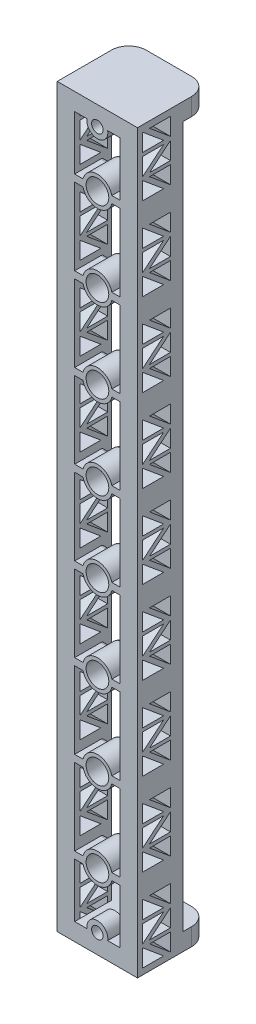
SolidWorks part; units mm, degrees
ref_plane "Front Plane" through (0, 0, 0) normal (0, 0, 1) x (1, 0, 0)
ref_plane "Top Plane" through (0, 0, 0) normal (0, 1, 0) x (1, 0, 0)
ref_plane "Right Plane" through (0, 0, 0) normal (1, 0, 0) x (0, 0, -1)
sketch "Sketch1" plane through (0, 0, 0) normal (0, 0, 1) x (1, 0, 0)
  line L0 (6.5, 100.5) -> (6.5, -100.5)
  line L1 (-11.5, 105.5) -> (11.5, 105.5)
  line L2 (-11.5, 105.5) -> (-11.5, -105.5)
  line L3 (-11.5, -105.5) -> (11.5, -105.5)
  line L4 (11.5, 105.5) -> (11.5, -105.5)
  line L5 (-11.5, 105.5) -> (11.5, -105.5) construction
  line L6 (-11.5, -105.5) -> (11.5, 105.5) construction
  line L7 (-6.5, -100.5) -> (6.5, -100.5)
  line L8 (-6.5, 100.5) -> (-6.5, -100.5)
  line L9 (-6.5, 100.5) -> (6.5, 100.5)
  point P0 (0, 0)
  dimension "D1" = 23
  dimension "D2" = 211
  dimension "D3" = 5
extrude "Boss-Extrude1" add sketch "Sketch1" along normal blind 13
sketch "Sketch7" plane through (0, 0, 13) normal (0, 0, 1) x (1, 0, 0)
  line L0 (0.0237, 87.6593) -> (0.0237, 80.2815) construction
  line L5 (-3.3958, 83) -> (-7.3958, 83)
  line L6 (7.4431, 85) -> (3.4431, 85)
  line L11 (-3.3958, 85) -> (-3.3958, 83)
  line L12 (-7.3958, 85) -> (-3.3958, 85)
  line L13 (3.4431, 85) -> (3.4431, 83)
  line L14 (3.4431, 83) -> (7.4431, 83)
  line L15 (7.4431, 83) -> (7.4431, 85)
  line L16 (-7.3958, 83) -> (-7.3958, 85)
  line L18 (11.5, 105.5) -> (-11.5, 105.5) construction
  circle A0 centre (0.0237, 84) radius 3.25
  circle A1 centre (0.0237, 84) radius 4.25
  point P5 (7.4431, 84)
  line M25 (-6.5, -100.5) -> (-6.5, 100.5)
  line M27 (6.5, 100.5) -> (6.5, -100.5)
  dimension "D1" = 6.5
  dimension "D2" = 8.5
  dimension "D3" = 20.5
  dimension "D4" = 4
  dimension "D5" = 2
extrude "Boss-Extrude5" add sketch "Sketch7" against normal blind 8.5 contours A1 L12 L5 M25 | L6 A1 L12 L11 L5 L14 L13 A0 | L12 A1 L5 L11 | L14 A1 L6 L13 | A1 L14 L6 M27 | L16 L5 L12 M25 | L14 L15 L6 M27 | L13 L14 L15 L6 region at (-3.2772, 84, 13) region at (-3.7921, 84, 13) region at (-5.3431, 84, 13) region at (-6.9479, 84, 13) region at (5.3668, 84, 13) region at (3.8394, 84, 13) region at (6.9715, 84, 13)
fillet "Fillet4" radius 1 6 edges at (-5.3035, 83, 4.5) (5.3272, 85, 4.5) (-5.3035, 85, 4.5) (0.0237, 88.25, 4.5) (5.3272, 83, 4.5) (0.0237, 79.75, 4.5)
pattern_linear "LPattern7" count 8 spacing 24 along (0, -1, 0) of "Boss-Extrude5", "Fillet4"
sketch "Sketch11" plane through (0, -105.5, 0) normal (0, -1, 0) x (-1, 0, 0)
  line L0 (6.5, -2.0313) -> (6.5, 0)
  line L2 (11.5, 0) -> (-11.5, 0) construction
  line L3 (11.5, -13) -> (11.5, 0) construction
  line L4 (8.5313, 0) -> (6.5, 0)
  line L5 (0, 0) -> (0, -13) construction
  line L6 (11.5, -13) -> (-11.5, -13) construction
  line L7 (-8.5313, 0) -> (-6.5, 0)
  line L8 (-6.5, -2.0313) -> (-6.5, 0)
  arc A0 (6.5, -2.0313) -> (8.5313, 0) centre (6.5, 0) ccw
  arc A1 (-6.5, -2.0313) -> (-8.5313, 0) centre (-6.5, 0) cw
  dimension "D1" = 5
ref_plane "Plane1" through (0, 0, 0) normal (-1, 0, 0) x (0, 0, 1)
ref_plane "Plane2" through (0, 0, 0) normal (0, 1, 0) x (1, 0, 0)
sketch "Sketch15" plane through (0, 105.5, 0) normal (0, 1, 0) x (1, 0, 0)
  line L0 (11.5, 0) -> (-11.5, 0)
  line L4 (11.5, 0) -> (4.4687, 0)
  line L5 (-11.5, 0) -> (-11.5, -13)
  line L6 (-11.5, -13) -> (11.5, -13)
  line L7 (11.5, -13) -> (11.5, 0)
  line L9 (-11.5, 0) -> (-11.5, -13)
  line L10 (-11.5, -13) -> (11.5, -13)
  line L11 (11.5, -13) -> (11.5, 0)
  line L21 (-6.5, 0) -> (-6.5, -2.0313)
  line L25 (-8.5313, 0) -> (-11.5, 0)
  line L26 (6.5, -2.0313) -> (6.5, 0)
  line L27 (6.5, 0) -> (-6.5, 0)
  arc A2 (-8.5313, 0) -> (-6.5, -2.0313) centre (-6.5, 0) ccw
  arc A6 (6.5, -2.0313) -> (4.4687, 0) centre (6.5, 0) ccw
  dimension "D1" = 0
extrude "Boss-Extrude8" add sketch "Sketch15" along normal blind 5
mirror "Mirror5" about plane through (0, 0, 0) normal (0, 1, 0) of "Boss-Extrude8"
sketch "Sketch19" plane through (-11.5, 0, 0) normal (-1, 0, 0) x (0, 0, 1)
  line L0 (13, 105.5) -> (0, 105.5) construction
  line L1 (13, 110.5) -> (13, -110.5) construction
  line L2 (0, 110.5) -> (0, -110.5) construction
  line L3 (0, 110.5) -> (13, 110.5) construction
  line L4 (13, 82.75) -> (0, 82.75) construction
  line L5 (13, 84.75) -> (0, 84.75) construction
  line L6 (0, 98.125) -> (13, 98.125) construction
  line L7 (9.5485, 103.625) -> (3.5485, 103.625)
  line L8 (3.5485, 103.625) -> (3.5485, 98.625)
  line L9 (3.5485, 98.625) -> (9.5485, 103.625)
  line L10 (11.5, 103.625) -> (11.5, 98.625)
  line L11 (11.5, 98.625) -> (5.5, 98.625)
  line L12 (5.5, 98.625) -> (11.5, 103.625)
  line L13 (0, 92.125) -> (13, 92.125) construction
  line L14 (0, 0) -> (13, 0) construction
  line L15 (11.5, 97.625) -> (5.5, 97.625)
  line L16 (11.5, 92.625) -> (11.5, 97.625)
  line L17 (5.5, 97.625) -> (11.5, 92.625)
  line L18 (3.5485, 92.625) -> (3.5485, 97.625)
  line L19 (9.5485, 92.625) -> (3.5485, 92.625)
  line L20 (3.5485, 97.625) -> (9.5485, 92.625)
  line L21 (11.5, 91.625) -> (11.5, 86.625)
  line L22 (5.5, 86.625) -> (11.5, 91.625)
  line L23 (11.5, 86.625) -> (5.5, 86.625)
  line L24 (9.5485, 91.625) -> (3.5485, 91.625)
  line L25 (3.5485, 86.625) -> (9.5485, 91.625)
  line L26 (3.5485, 91.625) -> (3.5485, 86.625)
  dimension "D1" = 5
  dimension "D2" = 5
  dimension "D3" = 2
  dimension "D4" = 1.2493
  dimension "D5" = 1.5
  dimension "D6" = 0.5
  dimension "D7" = 1.875
  dimension "D8" = 6
  dimension "D9" = 0.5
extrude "Cut-Extrude7" cut sketch "Sketch19" against normal blind 5
pattern_linear "LPattern10" count 9 spacing 23.8 along (0, -1, 0) of "Cut-Extrude7"
ref_plane "Plane3" through (0, 0, 0) normal (-1, 0, 0) x (0, 0, 1)
mirror "Mirror7" about plane through (0, 0, 0) normal (-1, 0, 0) of "LPattern10", "Cut-Extrude7"
sketch "Sketch22" plane through (0, 0, 0) normal (0, 0, -1) x (-1, 0, 0)
  line L0 (11.5, 110.5) -> (11.5, -110.5) construction
  line L1 (-11.5, 110.5) -> (11.5, 110.5)
  line L2 (-11.5, 110.5) -> (-11.5, 105.5)
  line L3 (-11.5, 105.5) -> (11.5, 105.5)
  line L4 (11.5, 110.5) -> (11.5, 105.5)
  line L6 (-11.5, -110.5) -> (11.5, -110.5)
  line L7 (-11.5, -110.5) -> (-11.5, -105.5)
  line L8 (-11.5, -105.5) -> (11.5, -105.5)
  line L9 (11.5, -110.5) -> (11.5, -105.5)
  dimension "D1" = 5
  dimension "D2" = 5
extrude "Cut-Extrude9" cut sketch "Sketch22" against normal through all
sketch "Sketch21" plane through (0, 0, 13) normal (0, 0, 1) x (1, 0, 0)
  line L1 (6.5, 100.5) -> (-6.5, 100.5) construction
  line L6 (-4.7323, 0) -> (3.9666, 0) construction
  line L11 (-2.5, 100.5) -> (2.5, 100.5)
  line L12 (-2.5, 100.5) -> (-2.5, 103.5)
  line L13 (-2.5, 103.5) -> (2.5, 103.5)
  line L14 (2.5, 100.5) -> (2.5, 103.5)
  line L15 (11.5, 105.5) -> (-11.5, 105.5) construction
  line L16 (-2.5, -103.5) -> (2.5, -103.5)
  line L17 (2.5, -100.5) -> (2.5, -103.5)
  line L18 (-2.5, -100.5) -> (2.5, -100.5)
  line L19 (-2.5, -100.5) -> (-2.5, -103.5)
  point P18 (0, 105.5)
  point P19 (0, 103.5)
  dimension "D3" = 3
  dimension "D4" = 5
extrude "Cut-Extrude8" [suppressed] cut sketch "Sketch21" against normal blind 5
fillet "Fillet7" [suppressed] radius 1
sketch "Sketch23" plane through (0, 0, 0) normal (0, 0, -1) x (-1, 0, 0)
  line L0 (11.5, 105.5) -> (11.5, -105.5) construction
  line L1 (-11.5, 105.5) -> (11.5, 105.5)
  line L2 (-11.5, 105.5) -> (-11.5, 100.5)
  line L3 (-11.5, 100.5) -> (11.5, 100.5)
  line L4 (11.5, 105.5) -> (11.5, 100.5)
  line L5 (-6.5, 100.5) -> (6.5, 100.5) construction
  line L6 (6.5, -100.5) -> (-6.5, -100.5) construction
  line L7 (-11.5, -105.5) -> (11.5, -105.5)
  line L8 (-11.5, -105.5) -> (-11.5, -100.5)
  line L9 (-11.5, -100.5) -> (11.5, -100.5)
  line L10 (11.5, -105.5) -> (11.5, -100.5)
extrude "Boss-Extrude9" add sketch "Sketch23" along normal blind 7.5
fillet "Fillet8" radius 5 4 edges at (11.5, 103, -7.5) (-11.5, 103, -7.5) (-11.5, -103, -7.5) (11.5, -103, -7.5)
sketch "Sketch25" plane through (0, -105.5, 0) normal (0, -1, 0) x (1, 0, 0)
  line L4 (-11.5, 13) -> (-11.5, -2.5) construction
  line L5 (-11.5, 13) -> (11.5, 13) construction
  line L6 (-9, -0.5) -> (-6, -0.5)
  line L7 (-6, -0.5) -> (-6, 2.5)
  line L8 (0, 2.725) -> (0, -1.8067) construction
  line L9 (6, -0.5) -> (6, 2.5)
  line L10 (9, -0.5) -> (6, -0.5)
  arc A0 (-6, 2.5) -> (-9, -0.5) centre (-6, -0.5) ccw
  arc A1 (6, 2.5) -> (9, -0.5) centre (6, -0.5) cw
  dimension "D1" = 13.5
  dimension "D2" = 5.5
  dimension "D3" = 3
extrude "Cut-Extrude11" cut sketch "Sketch25" against normal up to surface (206 mm away) from surface up to face at (0, 100.5, 3.3957) starting at face at (0, -100.5, 3.769)
sketch "Sketch26" plane through (0, 0, 13) normal (0, 0, 1) x (1, 0, 0)
  line L0 (0, 100) -> (0, -100) construction
  circle A0 centre (0, -100) radius 3
  circle A1 centre (0, 100) radius 3
  point P4 (0, 0)
  dimension "D2" = 6
  dimension "D1" = 200
extrude "Boss-Extrude10" add sketch "Sketch26" against normal blind 5
sketch "Sketch27" plane through (0, 0, 13) normal (0, 0, 1) x (1, 0, 0)
  circle A0 centre (0, -100) radius 1.65
  circle A1 centre (0, 100) radius 1.65
  dimension "D1" = 3.3
extrude "Cut-Extrude12" cut sketch "Sketch27" against normal through all
